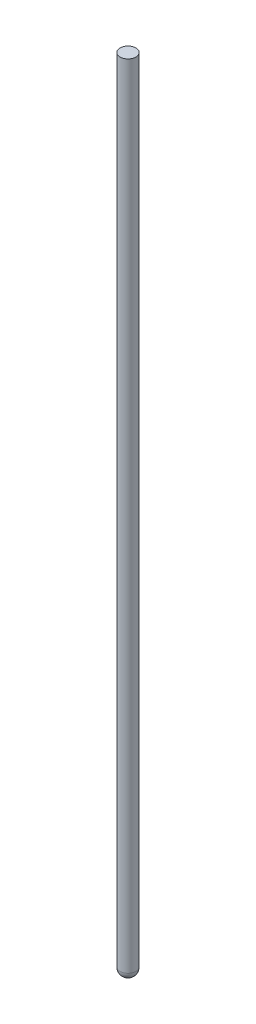
SolidWorks part; units mm, degrees
material "1060 Alloy"
ref_plane "Front Plane" through (0, 0, 0) normal (0, 0, 1) x (1, 0, 0)
ref_plane "Top Plane" through (0, 0, 0) normal (0, 1, 0) x (1, 0, 0)
ref_plane "Right Plane" through (0, 0, 0) normal (1, 0, 0) x (0, 0, -1)
sketch "Sketch1" plane through (0, 0, 0) normal (0, 0, 1) x (1, 0, 0)
  line L0 (0, 0) -> (0, -51.9041) construction
  line L1 (0, 0) -> (0.5, 0)
  line L2 (0, 0) -> (0, 50)
  line L3 (0, 50) -> (0.5, 50)
  line L4 (0.5, 0) -> (0.5, 50)
  dimension "D1" = 50
  dimension "D2" = 1
revolve "Revolve1" add sketch "Sketch1" angle 360 about L0
dome "Dome1" faces to dome 1 distance 0.5 reverse direction no elliptical dome no face at (0, 0, 0.5) parameters "D1"=0.5
